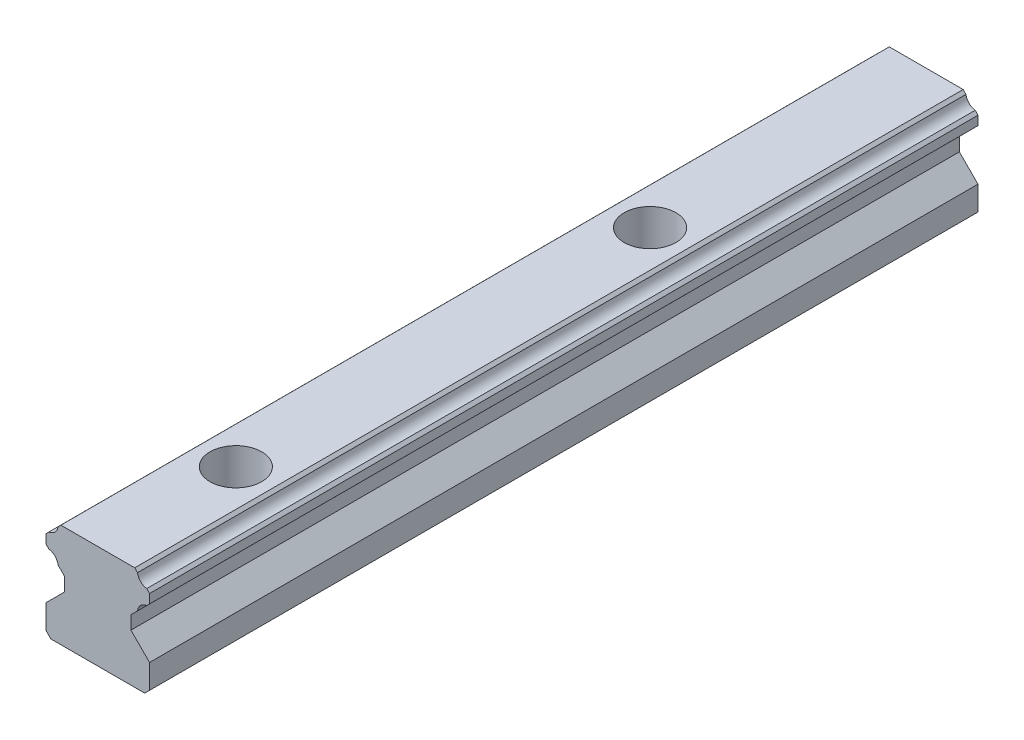
SolidWorks part; units mm, degrees
ref_plane "Front Plane" through (0, 0, 0) normal (0, 0, 1) x (1, 0, 0)
ref_plane "Top Plane" through (0, 0, 0) normal (0, 1, 0) x (1, 0, 0)
ref_plane "Right Plane" through (0, 0, 0) normal (1, 0, 0) x (0, 0, -1)
sketch "Sketch1" plane through (-20, 0, 0) normal (0, 0, 1) x (1, 0, 0)
  line L0 (12.5, 0.7) -> (13.2, 0)
  line L1 (13.2, 0) -> (26.8, 0)
  line L2 (27.5, 4.2) -> (27.5, 0.7)
  line L3 (24.8, 6.9) -> (27.5, 4.2)
  line L4 (24.8, 8.84) -> (24.8, 6.9)
  line L5 (25.7559, 9.7942) -> (24.8, 8.84)
  line L6 (27.5, 11.54) -> (27.0943, 11.1343)
  line L7 (27.5, 12.85) -> (27.5, 11.54)
  line L8 (27.0943, 13.2684) -> (27.5, 12.85)
  line L9 (25.35, 15) -> (25.7559, 14.5941)
  line L10 (27.5, 0.7) -> (26.8, 0)
  line L11 (25.35, 15) -> (14.65, 15)
  line L12 (14.65, 15) -> (14.2441, 14.5941)
  line L13 (12.9057, 13.2684) -> (12.5, 12.85)
  line L14 (12.5, 12.85) -> (12.5, 11.54)
  line L15 (12.5, 11.54) -> (12.9057, 11.1343)
  line L16 (14.2441, 9.7942) -> (15.2, 8.84)
  line L17 (15.2, 8.84) -> (15.2, 6.9)
  line L18 (15.2, 6.9) -> (12.5, 4.2)
  line L19 (12.5, 4.2) -> (12.5, 0.7)
  line L20 (20, 15) -> (20, 0) construction
  arc A0 (27.0943, 11.1343) -> (25.7559, 9.7942) centre (27.3023, 9.5882) ccw
  arc A1 (25.7559, 14.5941) -> (27.0943, 13.2684) centre (27.3003, 14.8148) ccw
  arc A2 (14.2441, 14.5941) -> (12.9057, 13.2684) centre (12.6997, 14.8148) cw
  arc A3 (12.9057, 11.1343) -> (14.2441, 9.7942) centre (12.6977, 9.5882) cw
  dimension "D14" = 1.56
  dimension "D1" = 15
  dimension "D2" = 0.7
  dimension "D3" = 0.7
  dimension "D4" = 4.2
  dimension "D5" = 6.9
  dimension "D6" = 8.84
  dimension "D7" = 4.8
  dimension "D8" = 5.7559
  dimension "D9" = 0.4059
  dimension "D10" = 0.4059
  dimension "D11" = 1.7316
  dimension "D12" = 2.15
  dimension "D13" = 3.46
  dimension "D15" = 7.0943
  dimension "D16" = 3.8657
  dimension "D17" = 5.2058
  dimension "D18" = 15
extrude "Extrude1" add sketch "Sketch1" against normal blind 120
sketch "Sketch2" plane through (0, 0, 0) normal (1, 0, 0) x (0, 0, -1)
  line L0 (20, 15) -> (23.75, 15)
  line L1 (23.75, 15) -> (23.75, 9.7)
  line L2 (23.75, 9.7) -> (22.25, 9.7)
  line L3 (22.25, 9.7) -> (22.25, 0)
  line L4 (22.25, 0) -> (20, 0)
  line L5 (20, 0) -> (20, 15) construction
  line L6 (20, 0) -> (20, 15) construction
  line L7 (20, 15) -> (20, 0)
  line L8 (120, 0) -> (0, 0) construction
  line L9 (120, 15) -> (0, 15) construction
  dimension "D1" = 5.3
  dimension "D2" = 7.5
  dimension "D3" = 4.5
  dimension "D4" = 20
revolve "Cut-Revolve1" cut sketch "Sketch2" angle 360 about L6 reverse direction yes
ref_axis "Axis1" through (0, 0, -168) along (0, 0, 1)
pattern_linear "LPattern1" count 2 spacing 60 along (0, 0, -1) of "Cut-Revolve1"
